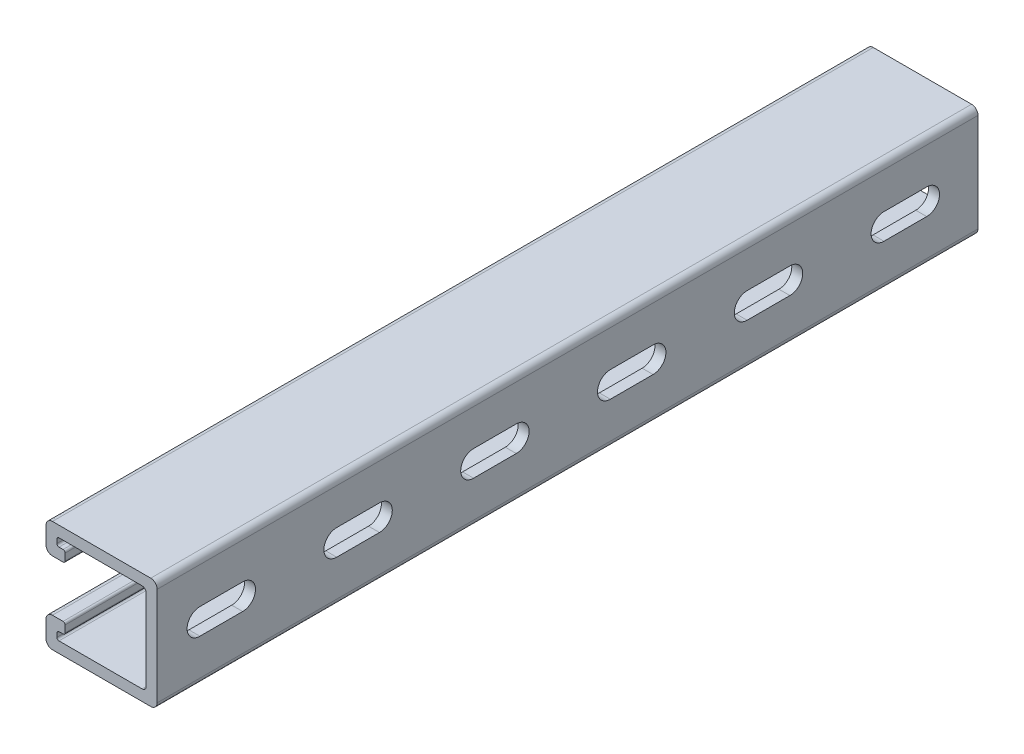
SolidWorks part; units mm, degrees
ref_plane "Front Plane" through (0, 0, 0) normal (0, 0, 1) x (1, 0, 0)
ref_plane "Top Plane" through (0, 0, 0) normal (0, 1, 0) x (1, 0, 0)
ref_plane "Right Plane" through (0, 0, 0) normal (1, 0, 0) x (0, 0, -1)
sketch "Sketch1" plane through (0, 0, 0) normal (0, 0, 1) x (1, 0, 0)
  line L0 (-13.5255, 9.525) -> (-18.2499, 9.525)
  line L1 (-20.6375, 11.9126) -> (-20.6375, 18.2499)
  line L2 (-18.2499, 20.6375) -> (18.2499, 20.6375)
  line L3 (20.6375, 18.2499) -> (20.6375, -18.2499)
  line L4 (18.2499, -20.6375) -> (-18.2499, -20.6375)
  line L5 (-20.6375, -18.2499) -> (-20.6375, -11.9126)
  line L6 (-18.2499, -9.525) -> (-13.5255, -9.525)
  line L7 (0, 0) -> (20.6375, 0) construction
  line L8 (0, 0) -> (0, 20.6375) construction
  arc A0 (-20.6375, 18.2499) -> (-18.2499, 20.6375) centre (-18.2499, 18.2499) cw
  arc A1 (-18.2499, 9.525) -> (-20.6375, 11.9126) centre (-18.2499, 11.9126) cw
  arc A2 (-20.6375, -11.9126) -> (-18.2499, -9.525) centre (-18.2499, -11.9126) cw
  arc A3 (-18.2499, -20.6375) -> (-20.6375, -18.2499) centre (-18.2499, -18.2499) cw
  arc A4 (20.6375, -18.2499) -> (18.2499, -20.6375) centre (18.2499, -18.2499) cw
  arc A5 (18.2499, 20.6375) -> (20.6375, 18.2499) centre (18.2499, 18.2499) cw
  point P14 (-20.6375, 20.6375)
  point P23 (20.6375, -20.6375)
  point P26 (20.6375, 20.6375)
  dimension "D4" = 2.3876
  dimension "D1" = 41.275
  dimension "D2" = 41.275
  dimension "D3" = 19.05
  dimension "D5" = 7.112
extrude "Extrude-Thin1" add sketch "Sketch1" against normal blind 304.8 thin thin type one direction wall 4.064
fillet "Fillet2" radius 0.762 8 edges at (-16.5735, 13.589, -152.4) (-16.5735, -16.5735, -152.4) (-16.5735, 16.5735, -152.4) (-13.5255, 13.589, -152.4) (-13.5255, 9.525, -152.4) (-13.5255, -9.525, -152.4) (-13.5255, -13.589, -152.4) (-16.5735, -13.589, -152.4)
fillet "Fillet3" radius 1.524 2 edges at (16.5735, 16.5735, -152.4) (16.5735, -16.5735, -152.4)
sketch "Sketch2" plane through (20.6375, 0, 0) normal (1, 0, 0) x (0, 0, -1)
  line L0 (15.875, 0) -> (31.75, 0) construction
  line L1 (15.875, 4.7625) -> (31.75, 4.7625)
  line L2 (15.875, -4.7625) -> (31.75, -4.7625)
  line L4 (15.875, 0) -> (0, 0) construction
  line L5 (23.8125, 0) -> (74.6125, 0) construction
  line L6 (0, 18.2499) -> (0, -18.2499) construction
  arc A0 (15.875, 4.7625) -> (15.875, -4.7625) centre (15.875, 0) ccw
  arc A1 (31.75, -4.7625) -> (31.75, 4.7625) centre (31.75, 0) ccw
  point P2 (23.8125, 0)
  dimension "D1" = 9.525
  dimension "D2" = 25.4
  dimension "Center Length" = 50.8
  dimension "D3" = 11.1125
extrude "Cut-Extrude1" cut sketch "Sketch2" against normal through all
pattern_linear "LPattern1" count 6 spacing 50.8 along (0, 0, -1) of "Cut-Extrude1"
sketch "Sketch3" plane through (0, 0, 0) normal (1, 0, 0) x (0, 0, -1)
  line L0 (0, 0) -> (304.8, 0) construction
  line L1 (304.8, 18.2499) -> (304.8, -18.2499) construction
  point P3 (101.6, 0)
  point P4 (203.2, 0)
  dimension "D1" = 101.6
  dimension "D2" = 101.6
equation "\"D3@LPattern1\" = \"Center Length@Sketch2\""
equation "\"D1@LPattern1\" = \"Length@Extrude-Thin1\"/\"Center Length@Sketch2\""
